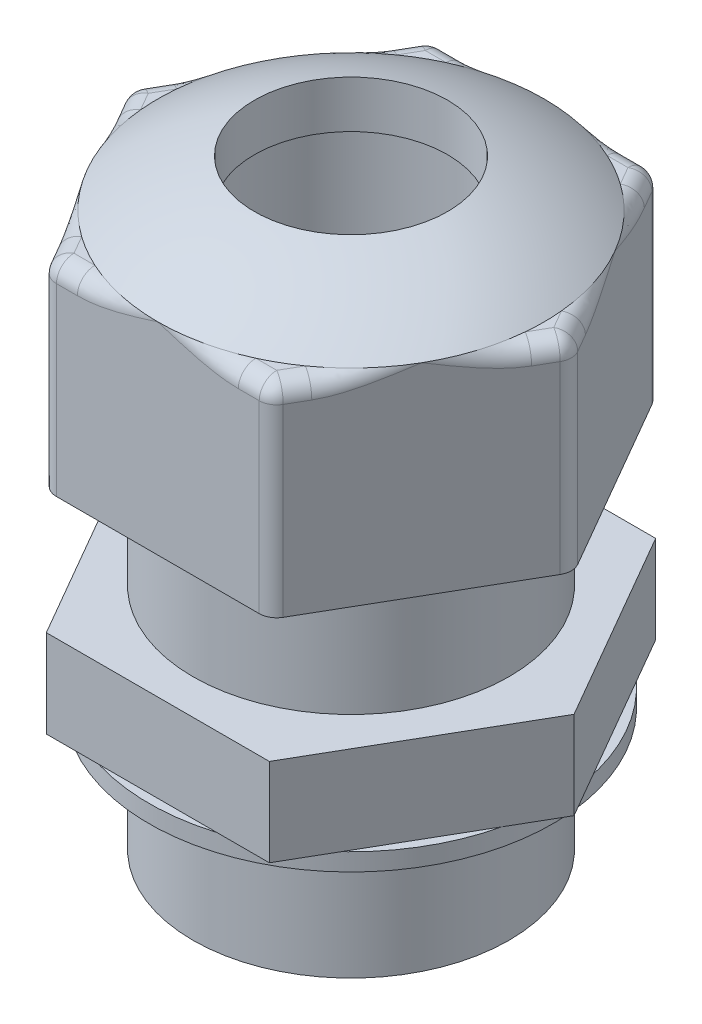
SolidWorks part; units mm, degrees
material "PE haute densité"
ref_plane "Plan de face" through (0, 0, 0) normal (0, 0, 1) x (1, 0, 0)
ref_plane "Plan de dessus" through (0, 0, 0) normal (0, 1, 0) x (1, 0, 0)
ref_plane "Plan de droite" through (0, 0, 0) normal (1, 0, 0) x (0, 0, -1)
sketch "Esquisse1" plane through (0, 0, 0) normal (0, 1, 0) x (1, 0, 0)
  line L1 (6.3509, -11) -> (12.7017, 0)
  line L2 (12.7017, 0) -> (6.3509, 11)
  line L3 (6.3509, 11) -> (-6.3509, 11)
  line L4 (-6.3509, 11) -> (-12.7017, 0)
  line L5 (-12.7017, 0) -> (-6.3509, -11)
  line L6 (-6.3509, -11) -> (6.3509, -11)
  circle A0 centre (0, 0) radius 11 construction
  dimension "D1" = 22
extrude "Extrusion1" add sketch "Esquisse1" along normal blind 5
sketch "Esquisse2" plane through (0, 0, 0) normal (0, -1, 0) x (1, 0, 0)
  circle A0 centre (0, 0) radius 9
  dimension "D1" = 18
extrude "Extrusion2" add sketch "Esquisse2" against normal blind 32 from offset 8
sketch "Esquisse3" plane through (0, 24, 0) normal (0, 1, 0) x (1, 0, 0)
  circle A0 centre (0, 0) radius 6.75
  dimension "D1" = 13.5
extrude "Extrusion3" cut sketch "Esquisse3" against normal through all
sketch "Esquisse4" plane through (0, 5, 0) normal (0, 1, 0) x (1, 0, 0)
  line L6 (-6.3509, -11) -> (6.3509, -11)
  line L7 (6.3509, -11) -> (12.7017, 0)
  line L8 (12.7017, 0) -> (6.3509, 11)
  line L9 (6.3509, 11) -> (-6.3509, 11)
  line L10 (-6.3509, 11) -> (-12.7017, 0)
  line L11 (-12.7017, 0) -> (-6.3509, -11)
  line L12 (-6.3509, -11) -> (6.3509, -11)
  line L13 (6.3509, -11) -> (12.7017, 0)
  line L14 (12.7017, 0) -> (6.3509, 11)
  line L15 (6.3509, 11) -> (-6.3509, 11)
  line L16 (-6.3509, 11) -> (-12.7017, 0)
  line L17 (-12.7017, 0) -> (-6.3509, -11)
  circle A0 centre (0, 0) radius 9 construction
  circle A1 centre (0, 0) radius 9
  dimension "D1" = 0
extrude "Extrusion4" add sketch "Esquisse4" along normal blind 11.5 from offset 7 separate body
sketch "Esquisse6" plane through (0, 0, 0) normal (1, 0, 0) x (0, 0, -1)
  line L0 (0, 23.5) -> (0, 27)
  line L1 (0, 23.5) -> (11, 23.5)
  arc A0 (0, 27) -> (11, 23.5) centre (0, 7.9643) cw
  dimension "D1" = 3.5
revolve "Révolution1" add sketch "Esquisse6" angle 360 about L0
fillet "Congé1" radius 1 18 edges at (7.9386, 23.5, 8.25) (11.114, 23.5, -2.75) (3.1754, 23.5, -11) (-7.9386, 23.5, -8.25) (-11.114, 23.5, 2.75) (3.1754, 23.5, 11) (-12.7017, 17.75, 0) (-6.3509, 17.75, -11) (6.3509, 17.75, -11) (-6.3509, 17.75, 11) (12.7017, 17.75, 0) (6.3509, 17.75, 11) (11.114, 23.5, 2.75) (7.9386, 23.5, -8.25) (-3.1754, 23.5, -11) (-11.114, 23.5, -2.75) (-7.9386, 23.5, 8.25) (-3.1754, 23.5, 11)
sketch "Esquisse7" plane through (0, -8, 0) normal (0, -1, 0) x (1, 0, 0)
  circle A0 centre (0, 0) radius 5.5
  dimension "D1" = 11
extrude "Extrusion5" cut sketch "Esquisse7" against normal through all
sketch "Esquisse8" plane through (0, 0, 0) normal (0, -1, 0) x (1, 0, 0)
  circle A0 centre (0, 0) radius 11.5
  circle A1 centre (0, 0) radius 9 construction
  circle A2 centre (0, 0) radius 9
  dimension "D1" = 23
extrude "Extrusion6" add sketch "Esquisse8" along normal blind 1 separate body
